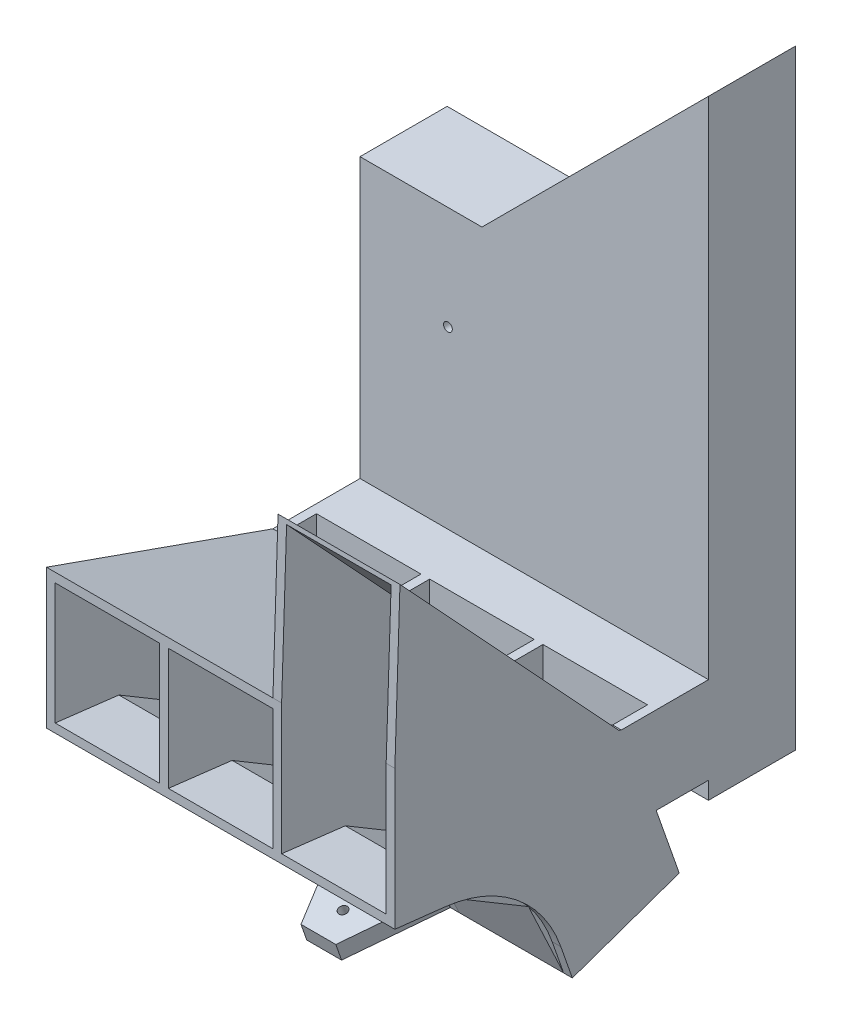
SolidWorks part; units mm, degrees
ref_plane "Přední rovina" through (0, 0, 0) normal (0, 0, 1) x (1, 0, 0)
ref_plane "Horní rovina" through (0, 0, 0) normal (0, 1, 0) x (1, 0, 0)
ref_plane "Pravá rovina" through (0, 0, 0) normal (1, 0, 0) x (0, 0, -1)
sketch "Skica1" plane through (0, 0, 0) normal (0, 0, 1) x (1, 0, 0)
  line L0 (0, 0) -> (200, 0)
  line L1 (200, 0) -> (200, 350)
  line L2 (200, 350) -> (70, 220)
  line L3 (70, 220) -> (0, 220)
  line L4 (0, 220) -> (0, 0)
  dimension "D1" = 350
  dimension "D2" = 200
  dimension "D3" = 70
  dimension "D4" = 220
extrude "Přidat vysunutím1" add sketch "Skica1" along normal blind 50
sketch "Skica7" plane through (0, 0, 50) normal (0, 0, 1) x (1, 0, 0)
  line L0 (0, 220) -> (0, 0) construction
  line L1 (0, 10) -> (200, 10)
  line L2 (0, 10) -> (0, 60)
  line L3 (0, 60) -> (200, 60)
  line L4 (200, 10) -> (200, 60)
  line L5 (200, 0) -> (200, 350) construction
  line L6 (0, 0) -> (200, 0) construction
  dimension "D1" = 50
  dimension "D2" = 10
extrude "Přidat vysunutím5" add sketch "Skica7" along normal blind 30
sketch "Skica9" plane through (0, 0, 0) normal (-1, 0, 0) x (0, 0, 1)
  line L0 (80, 10) -> (66.7748, -27.7504)
  line L2 (66.7748, -27.7504) -> (128.1192, -49.2414)
  line L3 (128.1192, -49.2414) -> (134.7318, -30.3662)
  line L4 (201.2747, 22.6803) -> (230, 25.9171)
  line L5 (230, 25.9171) -> (230, 105.9171)
  line L6 (230, 105.9171) -> (100, 60)
  line L7 (100, 60) -> (80, 60)
  line L8 (80, 60) -> (80, 10)
  arc A0 (134.7318, -30.3662) -> (201.2747, 22.6803) centre (210.2326, -56.8166) cw
  dimension "D1" = 80
  dimension "D2" = 65
  dimension "D3" = 80
  dimension "D4" = 20
  dimension "D5" = 130
  dimension "D6" = 40
  dimension "D7" = 20
  dimension "D8" = 160.693
extrude "Přidat vysunutím6" add sketch "Skica9" against normal blind 5
pattern_linear "LinPole1" count 4 spacing 65 along (1, 0, 0) of "Přidat vysunutím6"
sketch "Skica12" plane through (5, 0, 0) normal (1, 0, 0) x (0, 0, -1)
  line L0 (-230, 105.9171) -> (-230, 100.6144)
  line L1 (-230, 25.9171) -> (-230, 105.9171) construction
  line L2 (-230, 100.6144) -> (-105.2203, 56.5411)
  line L3 (-105.2203, 56.5411) -> (-71.4968, -29.4047)
  line L4 (-66.7748, -27.7504) -> (-128.1192, -49.2414) construction
  line L5 (-71.4968, -29.4047) -> (-66.7748, -27.7504)
  line L6 (-66.7748, -27.7504) -> (-101.4004, 60.4946)
  line L7 (-230, 105.9171) -> (-100, 60) construction
  line L8 (-101.4004, 60.4946) -> (-230, 105.9171)
  line L9 (-230, 25.9171) -> (-230, 30.9529)
  line L10 (-230, 30.9529) -> (-193.4216, 26.5716)
  line L11 (-193.4216, 26.5716) -> (-144.4818, -2.5962)
  line L12 (-144.4818, -2.5962) -> (-123.3759, -47.5797)
  line L13 (-123.3759, -47.5797) -> (-128.1192, -49.2414)
  line L14 (-128.1192, -49.2414) -> (-148.3576, -6.1069)
  line L15 (-148.3576, -6.1069) -> (-195.0698, 21.7333)
  line L16 (-195.0698, 21.7333) -> (-230, 25.9171)
  line L17 (-201.2747, 22.6803) -> (-230, 25.9171) construction
  arc A0 (-134.7318, -30.3662) -> (-201.2747, 22.6803) centre (-210.2326, -56.8166) ccw construction
  dimension "D1" = 5
  dimension "D2" = 5
  dimension "D3" = 94.7952
  dimension "D4" = 5
  dimension "D5" = 5
  dimension "D6" = 5
  dimension "D7" = 35.1798
  dimension "D8" = 54.3793
extrude "Přidat vysunutím10" add sketch "Skica12" along normal blind 60
pattern_linear "LinPole3" count 3 spacing 65 along (1, 0, 0) of "Přidat vysunutím10"
sketch "Skica16" plane through (0, 0, 230) normal (0, 0, 1) x (1, 0, 0)
  line L0 (165, 30.9529) -> (165, 287.5295) construction
  line L1 (195, 30.9529) -> (135, 30.9529) construction
  line L2 (100, 30.9529) -> (100, 240.3599) construction
  line L3 (130, 30.9529) -> (70, 30.9529) construction
  line L4 (35, 30.9529) -> (35, 225.5826) construction
  line L5 (65, 30.9529) -> (5, 30.9529) construction
  line L7 (133.4722, 193.1032) -> (194.1802, 193.1032)
  line L8 (133.4722, 193.1032) -> (133.4722, 128.1032)
  line L9 (133.4722, 128.1032) -> (194.1802, 128.1032)
  line L10 (194.1802, 193.1032) -> (194.1802, 128.1032)
  line L11 (133.4722, 193.1032) -> (194.1802, 128.1032) construction
  line L12 (133.4722, 128.1032) -> (194.1802, 193.1032) construction
  circle A0 centre (50.4595, 160.6032) radius 113.3667
  point P14 (163.8262, 160.6032)
  dimension "D1" = 65
sketch "Skica17" plane through (0, 21.9418, -7.75) normal (0, 0.9429, -0.333) x (1, 0, 0)
  line L0 (200, -252.1447) -> (200, -114.2738) construction
  line L1 (195, -252.1447) -> (135, -252.1447)
  line L2 (195, -252.1447) -> (195, -119.8147)
  line L3 (195, -119.8147) -> (135, -119.8147)
  line L4 (135, -252.1447) -> (135, -119.8147)
  line L6 (200, -252.1447) -> (0, -252.1447) construction
  dimension "D1" = 60
  dimension "D2" = 5
  dimension "D3" = 132.33
  dimension "D4" = 0
extrude "Odebrat vysunutím3" cut sketch "Skica17" against normal blind 10
sketch "Skica18" plane through (135, 0, 0) normal (1, 0, 0) x (0, 0, -1)
  line L0 (-101.4004, 60.4946) -> (-227.0714, 195.8695)
  line L1 (-227.0714, 195.8695) -> (-230, 105.9171)
  line L2 (-230, 105.9171) -> (-101.4004, 60.4946)
  dimension "D1" = 90
  dimension "D2" = 184.7148
extrude "Přidat vysunutím12" add sketch "Skica18" against normal blind 5
pattern_linear "LinPole4" count 2 spacing 65 along (1, 0, 0) of "Přidat vysunutím12"
sketch "Skica19" plane through (135, 0, 0) normal (1, 0, 0) x (0, 0, -1)
  line L0 (-227.0714, 195.8695) -> (-101.4004, 60.4946)
  line L1 (-101.4004, 60.4946) -> (-105.2246, 61.8454)
  line L2 (-105.2246, 61.8454) -> (-227.1585, 193.1946)
  line L3 (-227.0714, 195.8695) -> (-230, 105.9171) construction
  line L4 (-227.1585, 193.1946) -> (-227.0714, 195.8695)
extrude "Přidat vysunutím13" add sketch "Skica19" along normal blind 60
sketch "Skica20" plane through (0, 0, 50) normal (0, 0, 1) x (1, 0, 0)
  circle A0 centre (50.4595, 160.6032) radius 2.5
  dimension "D1" = 5
extrude "Odebrat vysunutím4" cut sketch "Skica20" against normal blind 10
sketch "Skica21" plane through (0, -3.8807, -1.3595) normal (0, -0.9438, -0.3306) x (1, 0, 0)
  line L0 (70, 137.1945) -> (90, 182.1945)
  line L1 (90, 182.1945) -> (110, 182.1945)
  line L2 (110, 182.1945) -> (130, 137.1945)
  line L3 (130, 137.1945) -> (70, 137.1945)
  point P4 (100, 182.1945)
  point P9 (100, 137.1945)
  dimension "D1" = 20
  dimension "D2" = 45
extrude "Přidat vysunutím15" add sketch "Skica21" against normal blind 10
sketch "Skica22" plane through (0, -3.8807, -1.3595) normal (0, -0.9438, -0.3306) x (1, 0, 0)
  line L1 (100, 206.8309) -> (100, 137.5945) construction
  line L2 (110, 182.1945) -> (90, 182.1945) construction
  circle A1 centre (100, 167.1945) radius 2.5
  dimension "D1" = 15
  dimension "D3" = 5
  dimension "D2" = 10
extrude "Odebrat vysunutím5" cut sketch "Skica22" against normal blind 10
